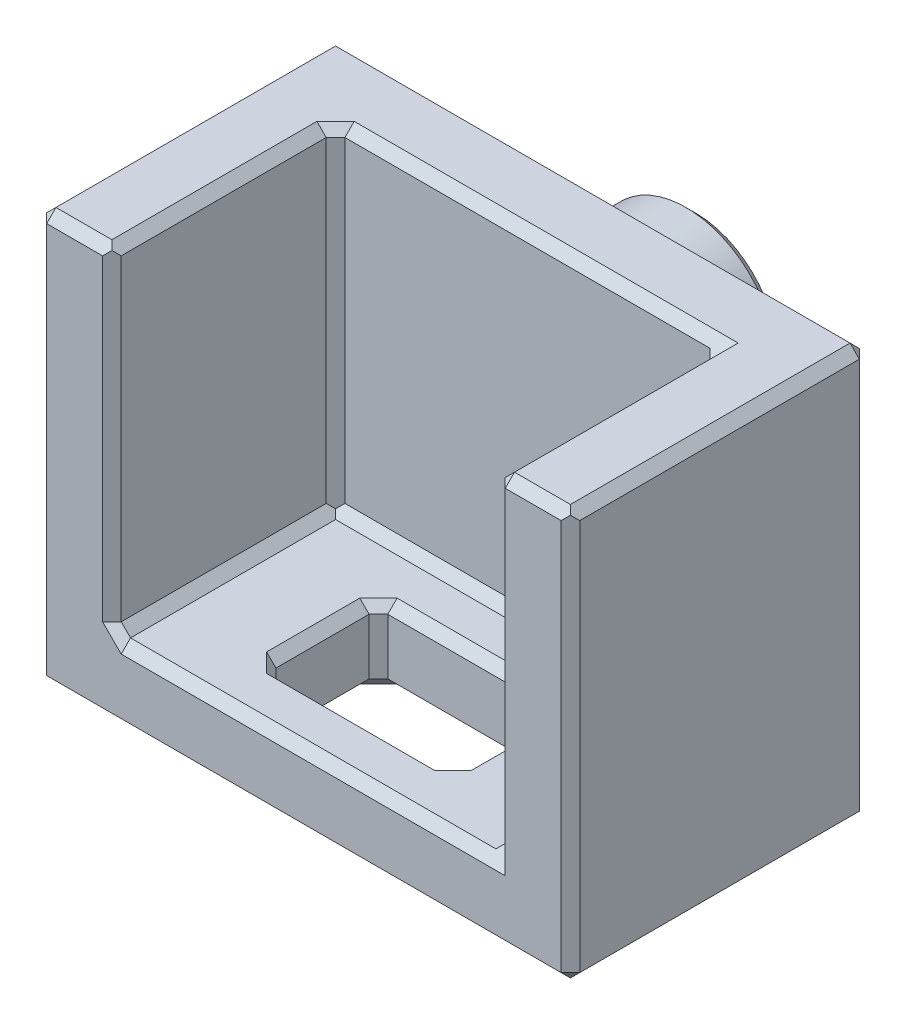
SolidWorks part; units mm, degrees
material "ABS"
ref_plane "Front Plane" through (0, 0, 0) normal (0, 0, 1) x (1, 0, 0)
ref_plane "Top Plane" through (0, 0, 0) normal (0, 1, 0) x (1, 0, 0)
ref_plane "Right Plane" through (0, 0, 0) normal (1, 0, 0) x (0, 0, -1)
sketch "Sketch1" plane through (0, 0, 0) normal (0, 1, 0) x (1, 0, 0)
  line L1 (-10.3, 2) -> (10.3, 2)
  line L2 (-10.3, 2) -> (-10.3, -2)
  line L3 (-10.3, -2) -> (10.3, -2)
  line L4 (10.3, 2) -> (10.3, -2)
  line L5 (-10.3, 2) -> (10.3, -2) construction
  line L6 (-10.3, -2) -> (10.3, 2) construction
  point P0 (0, 0)
  dimension "D1" = 4
  dimension "D2" = 20.6
extrude "Boss-Extrude1" add sketch "Sketch1" along normal blind 18
sketch "Sketch2" plane through (-10.3, 0, 0) normal (-1, 0, 0) x (0, 0, 1)
  line L1 (-2, 0) -> (14, 0)
  line L2 (-2, 0) -> (-2, 18)
  line L3 (-2, 18) -> (14, 18)
  line L4 (14, 0) -> (14, 18)
  dimension "D1" = 16
  dimension "D2" = 18
ref_plane "Plane1" through (0, 0, 0) normal (-1, 0, 0) x (0, 0, 1)
extrude "Boss-Extrude3" add sketch "Sketch2" along normal blind 4
mirror "Mirror1" about plane through (0, 0, 0) normal (-1, 0, 0) of "Boss-Extrude3"
sketch "Sketch3" plane through (0, 0, 2) normal (0, 0, 1) x (1, 0, 0)
  line L0 (10.3, 18) -> (10.3, 0) construction
  line L1 (-10.3, 0) -> (10.3, 0)
  line L2 (-10.3, 0) -> (-10.3, 4)
  line L3 (-10.3, 4) -> (10.3, 4)
  line L4 (10.3, 0) -> (10.3, 4)
  dimension "D1" = 4
extrude "Boss-Extrude4" add sketch "Sketch3" along normal up to surface (12 mm away) up to face at (-12.3, 9, 14)
sketch "Sketch4" plane through (0, 0, -2) normal (0, 0, -1) x (-1, 0, 0)
  line L0 (0, -55) -> (0, 55) construction
  circle A0 centre (0, 14) radius 4.9
  dimension "D1" = 9.8
  dimension "D2" = 14
extrude "Boss-Extrude5" add sketch "Sketch4" along normal blind 5
sketch "Sketch5" plane through (0, 4, 0) normal (0, 1, 0) x (1, 0, 0)
  line L0 (0, 55) -> (0, -55) construction
  line L1 (-5, -5) -> (5, -5)
  line L2 (-5, -5) -> (-5, -11)
  line L3 (-5, -11) -> (5, -11)
  line L4 (5, -5) -> (5, -11)
  line L5 (-5, -5) -> (5, -11) construction
  line L6 (-5, -11) -> (5, -5) construction
  line L7 (10.3, -2) -> (-10.3, -2) construction
  point P0 (0, -8)
  dimension "D1" = 6
  dimension "D2" = 10
  dimension "D3" = 3
extrude "Cut-Extrude1" cut sketch "Sketch5" against normal blind 10
sketch "Sketch6" plane through (0, 18, 0) normal (0, 1, 0) x (1, 0, 0)
  line L10 (-10.3, -2) -> (10.3, -2)
  line L11 (10.3, -2) -> (10.3, -14)
  line L12 (10.3, -14) -> (14.3, -14)
  line L13 (14.3, -14) -> (14.3, 2)
  line L14 (14.3, 2) -> (2.8302, 2)
  line L15 (2.8302, 2) -> (-2.8302, 2)
  line L16 (-2.8302, 2) -> (-14.3, 2)
  line L17 (-14.3, 2) -> (-14.3, -14)
  line L18 (-14.3, -14) -> (-10.3, -14)
  line L19 (-10.3, -14) -> (-10.3, -2)
  line L20 (-10.3, -2) -> (10.3, -2)
  line L21 (10.3, -2) -> (10.3, -14)
  line L22 (10.3, -14) -> (14.3, -14)
  line L23 (14.3, -14) -> (14.3, 2)
  line L24 (14.3, 2) -> (2.8302, 2)
  line L25 (2.8302, 2) -> (-2.8302, 2)
  line L26 (-2.8302, 2) -> (-14.3, 2)
  line L27 (-14.3, 2) -> (-14.3, -14)
  line L28 (-14.3, -14) -> (-10.3, -14)
  line L29 (-10.3, -14) -> (-10.3, -2)
  dimension "D1" = 0
extrude "Boss-Extrude6" add sketch "Sketch6" along normal blind 4
chamfer "Chamfer1" distance 0.5 angle 45 28 edges at (0, 4, 5) (5, 4, 8) (-5, 4, 8) (0, 4, 11) (-5, 2, 5) (-5, 2, 11) (5, 2, 11) (0, 0, 5) (-5, 0, 8) (0, 0, 11) (5, 0, 8) (-4.9, 14, -7) (14.3, 22, 6) (0, 22, -2) (14.3, 11, -2) (14.3, 11, 14) (14.3, 0, 6) (-14.3, 11, -2) (0, 0, 14) (-14.3, 0, 6) (0, 0, -2) (0, 22, 2) (0, 4, 14) (-10.3, 22, 8) (-10.3, 13, 14) (-10.3, 4, 8) (-10.3, 13, 2) (-4.9, 14, -2)
chamfer "Chamfer2" distance 0.5 angle 45 10 edges at (5, 2, 5) (12.05, 22, 14) (10.3, 22, 7.75) (10.3, 12.75, 14) (0.25, 4, 2) (10.3, 4, 7.75) (10.3, 12.75, 2) (-12.55, 22, 14) (-14.3, 11.25, 14) (-14.3, 22, 6.25)
